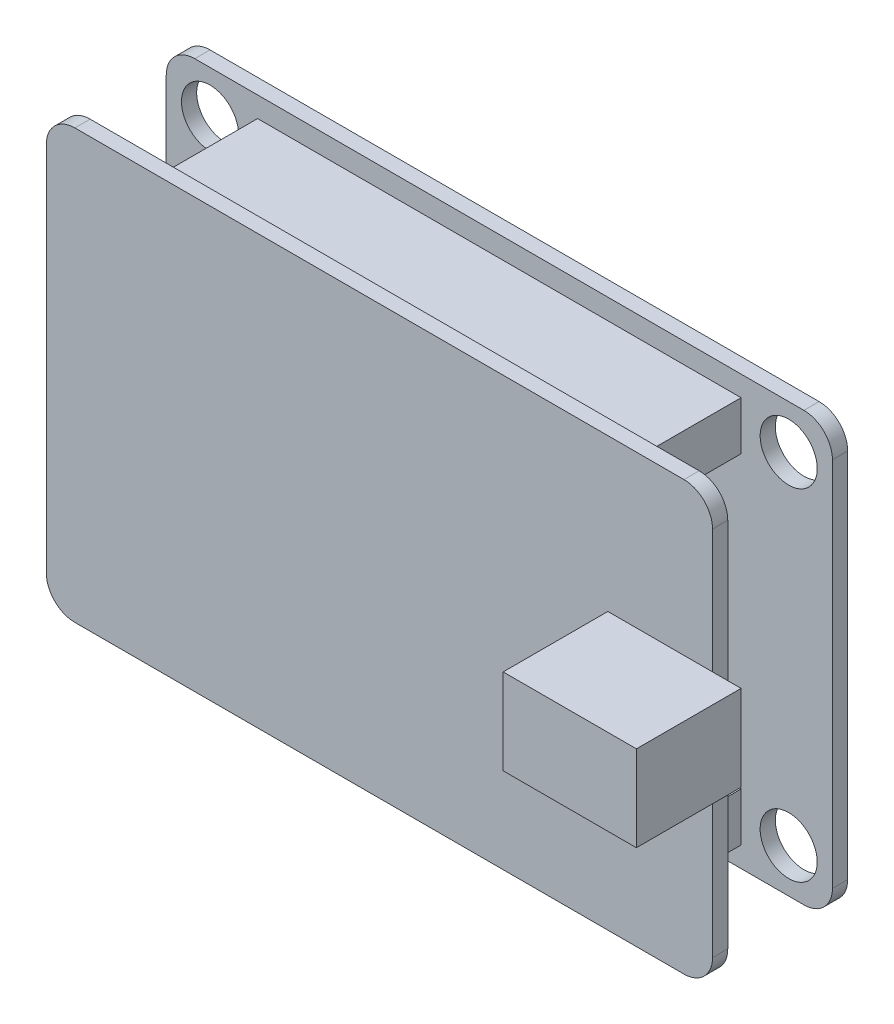
SolidWorks part; units mm, degrees
ref_plane "前视基准面" through (0, 0, 0) normal (0, 0, 1) x (1, 0, 0)
ref_plane "上视基准面" through (0, 0, 0) normal (0, 1, 0) x (1, 0, 0)
ref_plane "右视基准面" through (0, 0, 0) normal (1, 0, 0) x (0, 0, -1)
other "Configuration Table"
sketch "草图1" plane through (0, 0, 0) normal (0, 0, 1) x (1, 0, 0)
  line L0 (0, -55) -> (0, 55) construction
  line L1 (-32, -22.5) -> (32, -22.5)
  line L2 (-35, -19.5) -> (-35, 19.5)
  line L3 (-32, 22.5) -> (32, 22.5)
  line L4 (35, -19.5) -> (35, 19.5)
  line L5 (-35, -22.5) -> (35, 22.5) construction
  line L6 (-35, 22.5) -> (35, -22.5) construction
  line L7 (55, 0) -> (-55, 0) construction
  circle A0 centre (-30.4, 17.9) radius 3
  circle A1 centre (30.4, 17.9) radius 3
  circle A2 centre (30.4, -17.9) radius 3
  circle A3 centre (-30.4, -17.9) radius 3
  arc A4 (32, -22.5) -> (35, -19.5) centre (32, -19.5) ccw
  arc A5 (-32, -22.5) -> (-35, -19.5) centre (-32, -19.5) cw
  arc A6 (35, 19.5) -> (32, 22.5) centre (32, 19.5) ccw
  arc A7 (-32, 22.5) -> (-35, 19.5) centre (-32, 19.5) ccw
  point P0 (0, 0)
  dimension "D3" = 60.8
  dimension "D5" = 3
  dimension "D1" = 45
  dimension "D2" = 70
  dimension "D4" = 35.8
extrude "凸台-拉伸1" add sketch "草图1" along normal blind 1.6
sketch "草图2" plane through (0, 0, 1.6) normal (0, 0, 1) x (1, 0, 0)
  line L0 (0.88, 0) -> (-0.88, 0) construction
  line L1 (-25.4, 20.35) -> (25.4, 20.35)
  line L2 (-25.4, 20.35) -> (-25.4, 15.25)
  line L3 (-25.4, 15.25) -> (25.4, 15.25)
  line L4 (25.4, 20.35) -> (25.4, 15.25)
  line L5 (-25.4, 20.35) -> (25.4, 15.25) construction
  line L6 (-25.4, 15.25) -> (25.4, 20.35) construction
  line L7 (-25.4, -15.25) -> (25.4, -15.25)
  line L8 (25.4, -20.35) -> (25.4, -15.25)
  line L9 (-25.4, -20.35) -> (25.4, -20.35)
  line L10 (-25.4, -20.35) -> (-25.4, -15.25)
  point P0 (0, 17.8)
  point P5 (0, 19.3221)
  dimension "D1" = 5.1
  dimension "D2" = 50.8
  dimension "D3" = 30.5
extrude "凸台-拉伸2" add sketch "草图2" along normal blind 11
sketch "草图3" plane through (0, 0, 12.6) normal (0, 0, 1) x (1, 0, 0)
  line L4 (35, -19.5) -> (35, 19.5)
  line L5 (32, 22.5) -> (-32, 22.5)
  line L6 (-35, 19.5) -> (-35, -19.5)
  line L7 (-32, -22.5) -> (32, -22.5)
  line L8 (35, -19.5) -> (35, 19.5)
  line L9 (32, 22.5) -> (-32, 22.5)
  line L10 (-35, 19.5) -> (-35, -19.5)
  line L11 (-32, -22.5) -> (32, -22.5)
  arc A4 (32, -22.5) -> (35, -19.5) centre (32, -19.5) ccw
  arc A5 (35, 19.5) -> (32, 22.5) centre (32, 19.5) ccw
  arc A6 (-32, 22.5) -> (-35, 19.5) centre (-32, 19.5) ccw
  arc A7 (-35, -19.5) -> (-32, -22.5) centre (-32, -19.5) ccw
  arc A8 (32, -22.5) -> (35, -19.5) centre (32, -19.5) ccw
  arc A9 (35, 19.5) -> (32, 22.5) centre (32, 19.5) ccw
  arc A10 (-32, 22.5) -> (-35, 19.5) centre (-32, 19.5) ccw
  arc A11 (-35, -19.5) -> (-32, -22.5) centre (-32, -19.5) ccw
  dimension "D1" = 0
extrude "凸台-拉伸3" add sketch "草图3" along normal blind 1.6
sketch "草图4" plane through (0, 0, 14.2) normal (0, 0, 1) x (1, 0, 0)
  line L0 (32, 22.5) -> (-32, 22.5) construction
  line L1 (24, 6.5) -> (38, 6.5)
  line L2 (24, 6.5) -> (24, -2.5)
  line L3 (24, -2.5) -> (38, -2.5)
  line L4 (38, 6.5) -> (38, -2.5)
  line L5 (24, 6.5) -> (38, -2.5) construction
  line L6 (24, -2.5) -> (38, 6.5) construction
  line L7 (35, -19.5) -> (35, 19.5) construction
  point P0 (31, 2)
  dimension "D1" = 16
  dimension "D2" = 9
  dimension "D3" = 11
  dimension "D4" = 14
extrude "凸台-拉伸4" add sketch "草图4" along normal blind 11
